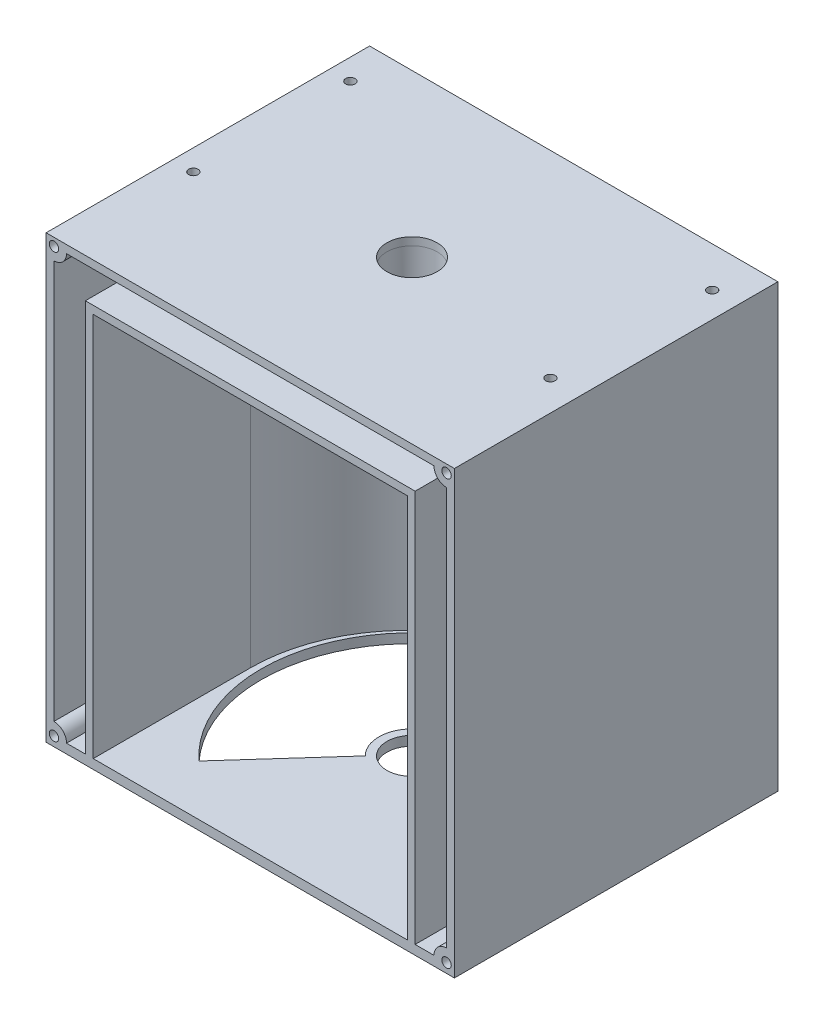
SolidWorks part; units mm, degrees
ref_plane "Front Plane" through (0, 0, 0) normal (0, 0, 1) x (1, 0, 0)
ref_plane "Top Plane" through (0, 0, 0) normal (0, 1, 0) x (1, 0, 0)
ref_plane "Right Plane" through (0, 0, 0) normal (1, 0, 0) x (0, 0, -1)
sketch "Sketch1" plane through (0, 0, 0) normal (0, 0, 1) x (1, 0, 0)
  line L9 (-104.732, 57.597) -> (-4.732, 57.597)
  line L10 (-104.732, 57.597) -> (-104.732, -92.403)
  line L11 (-104.732, -92.403) -> (-4.732, -92.403)
  line L12 (-4.732, 57.597) -> (-4.732, -92.403)
  line L13 (-107.232, 60.097) -> (-2.232, 60.097)
  line L14 (-107.232, 60.097) -> (-107.232, -94.903)
  line L15 (-107.232, -94.903) -> (-2.232, -94.903)
  line L16 (-2.232, 60.097) -> (-2.232, -94.903)
  dimension "D1" = 150
  dimension "D2" = 100
  dimension "D3" = 2.5
  dimension "D4" = 2.5
  dimension "D5" = 2.5
  dimension "D6" = 2.5
extrude "Boss-Extrude2" add sketch "Sketch1" against normal blind 3 and the other way blind 2 contours L14 L15 L16 L13
extrude "Boss-Extrude3" add sketch "Sketch1<5>" along normal blind 100
sketch "Sketch1<5>" plane through (0, 0, 0) normal (0, 0, 1) x (1, 0, 0) same geometry as "Sketch1"
sketch "Sketch4" plane through (0, -94.903, 0) normal (0, -1, 0) x (1, 0, 0)
  line L2 (-104.732, 50) -> (-104.732, 2)
  line L3 (-104.732, 2) -> (-4.732, 2)
  line L4 (-4.732, 50) -> (-4.732, 2)
  arc A0 (-104.732, 50) -> (-4.732, 50) centre (-54.732, 50) ccw
extrude "Boss-Extrude5" add sketch "Sketch4" against normal blind 153 contours A0 L3 L4 | A0 L2 L3 region at (-95.2199, -94.903, 12.9915) region at (-14.2441, -94.903, 12.9915)
extrude "Cut-Extrude1" cut sketch "Sketch4<3>" against normal blind 152.5 contours L3 A0 region at (-54.732, -94.903, 1.1986)
sketch "Sketch4<3>" plane through (0, -94.903, 0) normal (0, -1, 0) x (1, 0, 0) same geometry as "Sketch4"
extrude "Boss-Extrude6" add sketch "Sketch4<4>" against normal blind 2.5 contours L3 A0 region at (-54.732, -94.903, 1.1986)
sketch "Sketch4<4>" plane through (0, -94.903, 0) normal (0, -1, 0) x (1, 0, 0) same geometry as "Sketch4"
sketch "Sketch5" plane through (0, -94.903, 0) normal (0, -1, 0) x (1, 0, 0)
  circle A0 centre (-54.732, 48.5) radius 8
extrude "Cut-Extrude2" cut sketch "Sketch5" against normal blind 162.5
sketch "Sketch13" plane through (0, 0, 100) normal (0, 0, 1) x (1, 0, 0)
  line L0 (-2.232, -94.903) -> (-2.232, 60.097) construction
  line L1 (7.768, 70.097) -> (-117.232, 70.097)
  line L2 (7.768, 70.097) -> (7.768, -92.403)
  line L3 (7.768, -94.903) -> (-117.232, -94.903)
  line L4 (-117.232, 70.097) -> (-117.232, -92.403)
  line L5 (-2.232, 60.097) -> (-107.232, 60.097) construction
  line L6 (-107.232, 60.097) -> (-107.232, -94.903) construction
  line L7 (-107.232, -94.903) -> (-2.232, -94.903) construction
  line L8 (-117.232, -92.403) -> (-107.232, -92.403)
  line L9 (10.268, 72.597) -> (-119.732, 72.597)
  line L10 (10.268, 72.597) -> (10.268, -94.903)
  line L11 (10.268, -94.903) -> (-119.732, -94.903)
  line L12 (-119.732, 72.597) -> (-119.732, -94.903)
  line L13 (-2.232, -92.403) -> (7.768, -92.403)
  line L14 (-104.732, -92.403) -> (-4.732, -92.403) construction
  line L15 (-107.232, 60.097) -> (-2.232, 60.097)
  line L16 (-107.232, 60.097) -> (-107.232, -94.903)
  line L17 (-107.232, -94.903) -> (-2.232, -94.903)
  line L18 (-2.232, 60.097) -> (-2.232, -94.903)
  line M9 (-107.232, 60.097) -> (-107.232, -94.903)
  line M11 (-2.232, -94.903) -> (-2.232, 60.097)
  line M12 (-2.232, 60.097) -> (-107.232, 60.097)
  dimension "D1" = 10
  dimension "D2" = 10
  dimension "D3" = 10
  dimension "D4" = 0
  dimension "D5" = 2.5
  dimension "D6" = 2.5
  dimension "D7" = 2.5
  dimension "D8" = 0
  dimension "D9" = 0
extrude "Boss-Extrude12" add sketch "Sketch13" against normal blind 3 contours L13 L3 L11 L10 L9 L12 L8 L4 L1 L2 M11 M9 | L13 L2 L1 L4 L8 M11 M9 M12 region at (5.7178, -11.153, 100) region at (-54.732, 72.2172, 100)
extrude "Boss-Extrude13" add sketch "Sketch13<4>" against normal blind 103 contours L13 L3 L11 L10 L9 L12 L8 L4 L1 L2 M11 M9 region at (-54.732, 72.2172, 100)
sketch "Sketch13<4>" plane through (0, 0, 100) normal (0, 0, 1) x (1, 0, 0) same geometry as "Sketch13"
sketch "Sketch14" plane through (0, 0, -3) normal (0, 0, -1) x (-1, 0, 0)
  line L0 (117.232, -92.403) -> (107.232, -92.403) construction
  line L1 (107.232, 60.097) -> (107.232, -92.403) construction
  line L2 (107.232, 60.097) -> (2.232, 60.097) construction
  line L3 (2.232, 60.097) -> (2.232, -92.403) construction
  line L4 (-10.268, -94.903) -> (119.732, -94.903)
  line L5 (119.732, -94.903) -> (119.732, 72.597)
  line L6 (119.732, 72.597) -> (-10.268, 72.597)
  line L7 (-10.268, 72.597) -> (-10.268, -94.903)
  line L8 (-10.268, -94.903) -> (119.732, -94.903)
  line L9 (119.732, -94.903) -> (119.732, 72.597)
  line L10 (119.732, 72.597) -> (-10.268, 72.597)
  line L11 (-10.268, 72.597) -> (-10.268, -94.903)
  line L12 (2.232, -92.403) -> (-7.768, -92.403) construction
  line L13 (-7.768, 70.097) -> (-7.768, -92.403) construction
  line L14 (-7.768, 70.097) -> (117.232, 70.097) construction
  line L15 (117.232, 70.097) -> (117.232, -92.403) construction
  line L16 (117.232, -92.403) -> (107.232, -92.403)
  line L17 (107.232, 60.097) -> (107.232, -92.403)
  line L18 (107.232, 60.097) -> (2.232, 60.097)
  line L19 (2.232, 60.097) -> (2.232, -92.403)
  line L20 (2.232, -92.403) -> (-7.768, -92.403)
  line L21 (-7.768, 70.097) -> (-7.768, -92.403)
  line L22 (-7.768, 70.097) -> (117.232, 70.097)
  line L23 (117.232, 70.097) -> (117.232, -92.403)
  dimension "D1" = 0
extrude "Boss-Extrude14" add sketch "Sketch14" against normal blind 3 contours L17 L16 L23 L22 L21 L20 L19 L18
extrude "Cut-Extrude7" cut sketch "Sketch13<5>" against normal blind 3 contours L13 L2 L1 L4 L8 M11 M9 M12 region at (5.7178, -11.153, 100)
sketch "Sketch13<5>" plane through (0, 0, 100) normal (0, 0, 1) x (1, 0, 0) same geometry as "Sketch13"
sketch "Sketch15" plane through (0, -94.903, 0) normal (0, -1, 0) x (1, 0, 0)
  line L1 (-119.732, 100) -> (10.268, 100)
  line L2 (-119.732, 100) -> (-119.732, -3)
  line L3 (-119.732, -3) -> (10.268, -3)
  line L4 (10.268, 100) -> (10.268, -3)
extrude "Cut-Extrude8" cut sketch "Sketch15" against normal blind 30 contours L3 L4 L1 L2
sketch "Sketch16" plane through (0, -64.903, 0) normal (0, -1, 0) x (1, 0, 0)
  line L1 (-119.732, 100) -> (10.268, 100)
  line L2 (-119.732, 100) -> (-119.732, -3)
  line L3 (-119.732, -3) -> (10.268, -3)
  line L4 (10.268, 100) -> (10.268, -3)
extrude "Boss-Extrude15" add sketch "Sketch16" along normal blind 3
extrude "Cut-Extrude9" cut sketch "Sketch5<2>" against normal blind 222
sketch "Sketch5<2>" plane through (0, -94.903, 0) normal (0, -1, 0) x (1, 0, 0) same geometry as "Sketch5"
sketch "Sketch18" plane through (0, -67.903, 0) normal (0, -1, 0) x (1, 0, 0)
  circle A0 centre (4.018, 80) radius 1.5
  circle A1 centre (4.018, 20) radius 1.5
  circle A2 centre (-113.482, 20) radius 1.5
  circle A3 centre (-113.482, 20) radius 3
  circle A4 centre (-113.482, 80) radius 1.5
  circle A5 centre (-113.482, 80) radius 3
  circle A6 centre (4.018, 80) radius 3
  circle A7 centre (4.018, 20) radius 3
extrude "Cut-Extrude11" cut sketch "Sketch18" against normal blind 5 contours A0 | A1 | A2 | A4
sketch "Sketch19" plane through (0, 60.097, 0) normal (0, 1, 0) x (1, 0, 0)
  circle A0 centre (-54.732, -48.5) radius 8.1
  circle A1 centre (-54.732, -48.5) radius 10.0208
extrude "Boss-Extrude17" add sketch "Sketch19" along normal up to surface (12.5 mm away) and the other way blind 7 up to face at (-62.732, 72.597, 48.5)
sketch "Sketch21" plane through (0, 72.597, 0) normal (0, 1, 0) x (1, 0, 0)
  circle A0 centre (0.6344, -59.7847) radius 1.5
  circle A1 centre (2.1344, -9.7847) radius 1.5
  circle A2 centre (-113.0777, -9.7847) radius 1.5
  circle A3 centre (-113.0777, -59.7847) radius 1.5
extrude "Cut-Extrude13" cut sketch "Sketch21" against normal blind 4
sketch "Sketch22" plane through (0, 0, 100) normal (0, 0, 1) x (1, 0, 0)
  line L0 (-117.232, -60.903) -> (-117.232, -64.903)
  line L1 (7.768, 70.097) -> (3.768, 70.097)
  line L2 (7.768, 70.097) -> (7.768, 66.097)
  line L3 (7.768, -64.903) -> (3.768, -64.903)
  line L4 (-117.232, 70.097) -> (-117.232, 66.097)
  line L5 (-113.232, -64.903) -> (-117.232, -64.903)
  line L6 (7.768, -60.903) -> (7.768, -64.903)
  line L7 (-113.232, 70.097) -> (-117.232, 70.097)
  arc A0 (3.768, 70.097) -> (7.768, 66.097) centre (7.768, 70.097) ccw
  circle A1 centre (7.768, 70.097) radius 1.5
  arc A2 (7.768, -60.903) -> (3.768, -64.903) centre (7.768, -64.903) ccw
  circle A3 centre (7.768, -64.903) radius 1.5
  arc A4 (-113.232, -64.903) -> (-117.232, -60.903) centre (-117.232, -64.903) ccw
  circle A5 centre (-117.232, -64.903) radius 1.5
  arc A6 (-117.232, 66.097) -> (-113.232, 70.097) centre (-117.232, 70.097) ccw
  circle A7 centre (-117.232, 70.097) radius 1.5
  line M5 (-107.232, -64.903) -> (-117.232, -64.903)
  line M6 (-117.232, -64.903) -> (-117.232, 70.097)
  line M7 (-117.232, 70.097) -> (7.768, 70.097)
  line M8 (7.768, 70.097) -> (7.768, -64.903)
extrude "Boss-Extrude19" add sketch "Sketch22" against normal blind 10 contours A7 A6 L7 M6 | A1 A0 L2 M7 | A3 A2 L3 M8 | A5 A4 L0 M5 region at (-115.3607, -63.0318, 100) region at (5.8967, -63.0318, 100) region at (5.8967, 68.2257, 100) region at (-115.3607, 68.2257, 100)
extrude "Cut-Extrude14" cut sketch "Sketch22<3>" against normal blind 10 contours A7 | A5 | A3 | A1
sketch "Sketch22<3>" plane through (0, 0, 100) normal (0, 0, 1) x (1, 0, 0) same geometry as "Sketch22"
sketch "Sketch23" plane through (0, -67.903, 0) normal (0, -1, 0) x (1, 0, 0)
  line L0 (-54.0542, 38.001) -> (-54.732, 0.5)
  line L1 (-87.2264, 83.8287) -> (-62.1714, 55.9393)
  arc A0 (-87.2264, 83.8287) -> (-54.732, 0.5) centre (-54.732, 48.5) ccw
  arc A1 (-62.1714, 55.9393) -> (-54.0542, 38.001) centre (-54.732, 48.5) ccw
  arc A2 (-63.232, 55.5) -> (-61.732, 57) centre (-63.232, 57) ccw construction
extrude "Cut-Extrude15" cut sketch "Sketch23" against normal blind 10
